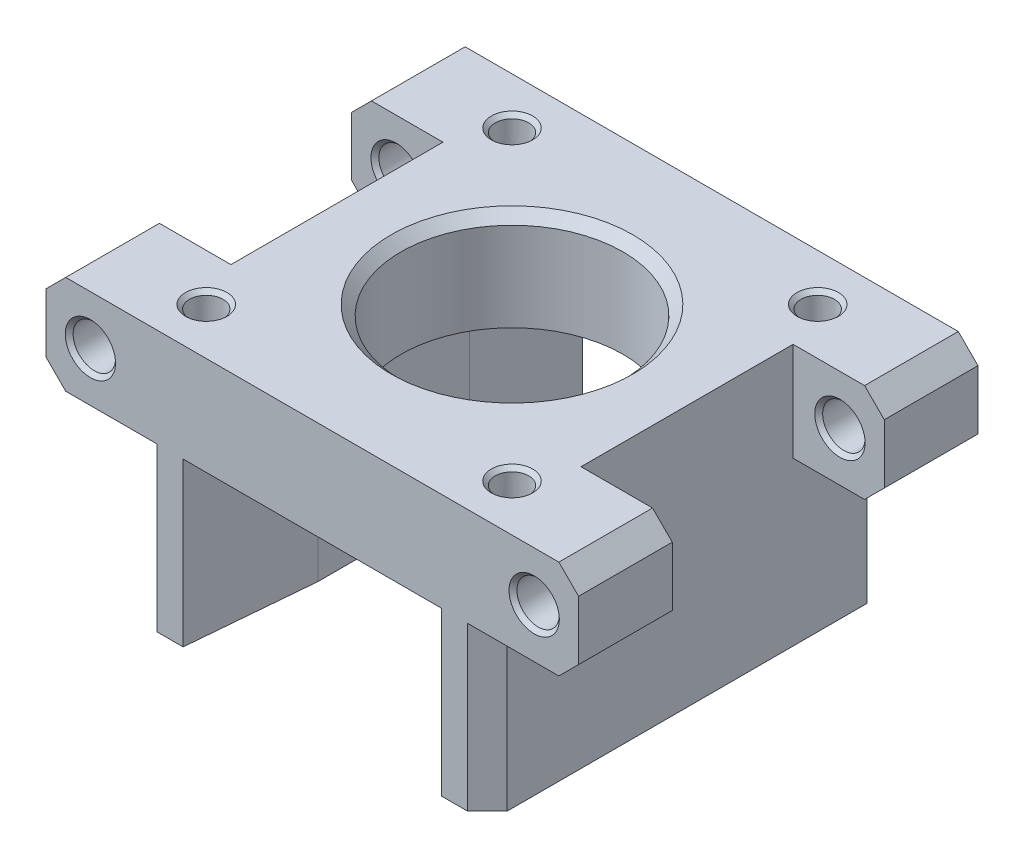
SolidWorks part; units mm, degrees
ref_plane "Top Plane" through (0, 0, 0) normal (0, 0, 1) x (1, 0, 0)
ref_plane "Front Plane" through (0, 0, 0) normal (0, 1, 0) x (1, 0, 0)
ref_plane "Right Plane" through (0, 0, 0) normal (1, 0, 0) x (0, 0, -1)
sketch "Sketch1" plane through (0, 0, 0) normal (0, 0, 1) x (1, 0, 0)
  line L0 (0, 0) -> (0, -10)
  line L1 (0, -10) -> (9.25, -10)
  line L2 (9.25, -10) -> (9.25, -26.5)
  line L3 (9.25, -26.5) -> (44.75, -26.5)
  line L4 (44.75, -26.5) -> (44.75, -10)
  line L5 (44.75, -10) -> (54, -10)
  line L6 (54, -10) -> (54, 0)
  line L7 (54, 0) -> (0, 0)
  dimension "D1" = 54
  dimension "D2" = 10
  dimension "D3" = 16.5
  dimension "D4" = 35.5
  dimension "D5" = 9.25
extrude "Boss-Extrude1" add sketch "Sketch1" along normal blind 40.5
sketch "Sketch2" plane through (0, 0, 40.5) normal (0, 0, 1) x (1, 0, 0)
  line L0 (54, 0) -> (0, 0) construction
  line L1 (0, 0) -> (0, -10) construction
  line L2 (54, -10) -> (54, 0) construction
  circle A0 centre (4.5, -5) radius 2.15
  circle A1 centre (49.5, -5) radius 2.15
  dimension "D1" = 4.3
  dimension "D2" = 4.3
  dimension "D3" = 5
  dimension "D4" = 4.5
  dimension "D5" = 5
  dimension "D6" = 4.5
extrude "Cut-Extrude1" cut sketch "Sketch2" against normal blind 40.5
sketch "Sketch3" plane through (0, -26.5, 0) normal (0, -1, 0) x (1, 0, 0)
  line L0 (9.25, 40.5) -> (9.25, 0) construction
  line L1 (9.25, 0) -> (44.75, 0) construction
  circle A0 centre (27, 20.25) radius 11.25
  dimension "D1" = 22.5
  dimension "D2" = 17.75
  dimension "D3" = 20.25
extrude "Cut-Extrude2" cut sketch "Sketch3" against normal blind 35.5
sketch "Sketch4" plane through (0, -26.5, 0) normal (0, -1, 0) x (1, 0, 0)
  line L1 (42.5, 4.75) -> (11.5, 4.75)
  line L2 (42.5, 4.75) -> (42.5, 35.75)
  line L3 (42.5, 35.75) -> (11.5, 35.75)
  line L4 (11.5, 4.75) -> (11.5, 35.75)
  line L5 (42.5, 4.75) -> (11.5, 35.75) construction
  line L6 (42.5, 35.75) -> (11.5, 4.75) construction
  point P0 (27, 20.25)
  dimension "D1" = 31
  dimension "D2" = 31
hole_wizard "M3 Clearance Hole1" positions "Sketch5" profile "Sketch7" hole size "M3" standard "DIN" end condition through all
sketch "Sketch5" plane through (0, -26.5, 0) normal (0, -1, 0) x (-1, 0, 0)
  point P0 (-11.5, -35.75)
  point P3 (-42.5, -35.75)
  point P6 (-42.5, -4.75)
  point P9 (-11.5, -4.75)
sketch "Sketch7" plane through (11.5, -26.5, 35.75) normal (1, 0, 0) x (0, 0, -1)
  line L0 (0, 0) -> (0, 26.5)
  line L1 (0, 26.5) -> (1.7, 26.5)
  line L2 (1.7, 26.5) -> (1.7, 0)
  line L5 (1.7, 0) -> (0, 0)
  line L11 (0, -6.35) -> (0, 107.95) construction
  dimension "Thru Hole Dia." = 3.4
  dimension "Thru Hole Depth" = 26.5
sketch "Sketch8" plane through (0, -26.5, 0) normal (0, -1, 0) x (1, 0, 0)
  line L0 (9.25, 40.5) -> (44.75, 40.5) construction
  line L1 (15, 40.5) -> (39, 40.5)
  line L2 (15, 40.5) -> (15, 0)
  line L3 (15, 0) -> (39, 0)
  line L4 (39, 40.5) -> (39, 0)
  line L5 (9.25, 0) -> (44.75, 0) construction
  circle A0 centre (11.5, 35.75) radius 1.7 construction
  circle A1 centre (42.5, 35.75) radius 1.7 construction
  dimension "D1" = 3.5
  dimension "D2" = 3.5
extrude "Cut-Extrude3" cut sketch "Sketch8" against normal up to surface (16.5 mm away) up to face at (4.625, -10, 20.25)
chamfer "Chamfer1" distance 1.1 angle 85 4 edges at (39, -18.25, 0) (15, -18.25, 0) (39, -18.25, 40.5) (15, -18.25, 40.5) first distance on face at (6.65, -5, 0) first distance on face at (27, -13.8333, 40.5)
sketch "Sketch9" plane through (0, 0, 0) normal (0, 1, 0) x (1, 0, 0)
  line L0 (0, -40.5) -> (0, 0) construction
  line L1 (0, -9.5) -> (9.25, -9.5)
  line L2 (0, -9.5) -> (0, -31)
  line L3 (0, -31) -> (9.25, -31)
  line L4 (9.25, -9.5) -> (9.25, -31)
  line L5 (54, -40.5) -> (54, 0) construction
  line L6 (54, -9.5) -> (44.75, -9.5)
  line L7 (54, -9.5) -> (54, -31)
  line L8 (54, -31) -> (44.75, -31)
  line L9 (44.75, -9.5) -> (44.75, -31)
  line L10 (54, 0) -> (0, 0) construction
  line L11 (54, -40.5) -> (0, -40.5) construction
  dimension "D1" = 9.25
  dimension "D2" = 9.5
  dimension "D3" = 9.5
  dimension "D4" = 9.25
  dimension "D5" = 9.5
  dimension "D6" = 9.5
extrude "Cut-Extrude4" cut sketch "Sketch9" against normal blind 10
chamfer "Chamfer4" distance 2 angle 45 8 edges at (0, 0, 4.75) (0, -10, 4.75) (0, 0, 35.75) (0, -10, 35.75) (54, -10, 4.75) (54, 0, 4.75) (54, -10, 35.75) (54, 0, 35.75)
chamfer "Chamfer6" distance 1 angle 45 1 edges at (27, 0, 9)
chamfer "Chamfer7" distance 0.4 angle 45 16 edges at (51.65, -5, 40.5) (51.65, -5, 31) (51.65, -5, 0) (47.35, -5, 9.5) (6.65, -5, 0) (2.35, -5, 9.5) (6.65, -5, 40.5) (6.65, -5, 31) (11.5, -26.5, 34.05) (11.5, 0, 34.05) (42.5, -26.5, 34.05) (42.5, 0, 34.05) (42.5, -26.5, 3.05) (42.5, 0, 3.05) (11.5, -26.5, 3.05) (11.5, 0, 3.05)
chamfer "Chamfer8" distance 2 angle 45 4 edges at (44.75, -18.25, 0) (44.75, -18.25, 40.5) (9.25, -18.25, 0) (9.25, -18.25, 40.5)
